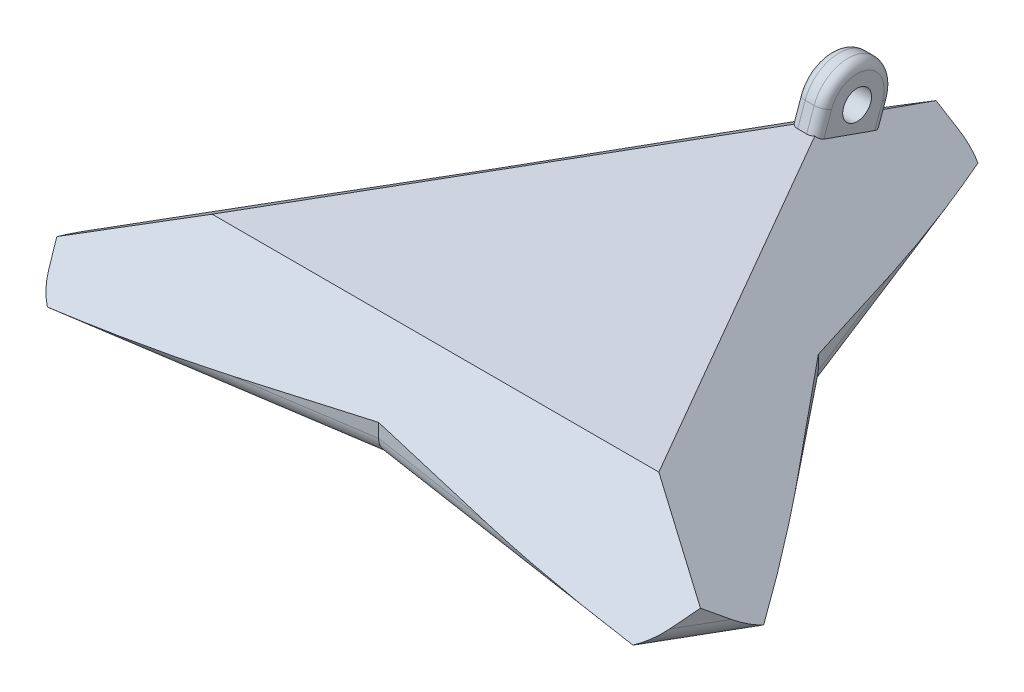
SolidWorks part; units mm, degrees
ref_plane "Front Plane" through (0, 0, 0) normal (0, 0, 1) x (1, 0, 0)
ref_plane "Top Plane" through (0, 0, 0) normal (0, 1, 0) x (1, 0, 0)
ref_plane "Right Plane" through (0, 0, 0) normal (1, 0, 0) x (0, 0, -1)
sketch "Sketch2" plane through (0, 0, 0) normal (0, 1, 0) x (1, 0, 0)
  line L0 (0, 51.9615) -> (-45, -25.9808)
  line L1 (-45, -25.9808) -> (45, -25.9808)
  line L2 (45, -25.9808) -> (0, 51.9615)
  line L3 (0, 0) -> (0, 51.9615) construction
  line L4 (45, -25.9808) -> (0, 0) construction
  line L5 (0, 0) -> (-45, -25.9808) construction
  line L6 (0, 0) -> (0, -25.9808) construction
  line L7 (0, 0) -> (22.5, 12.9904) construction
  line L8 (0, 0) -> (-22.5, 12.9904) construction
  line L9 (10, 34.641) -> (0, 28.8675) construction
  line L10 (0, 28.8675) -> (-10, 34.641) construction
  dimension "D1" = 20
sketch "Sketch3" plane through (0, 0, 0) normal (1, 0, 0) x (0, 0, -1)
  line L0 (-25.9808, 0) -> (-17.3205, 24.4949) construction
  line L1 (-17.3205, 24.4949) -> (0, 18.3712) construction
  line L2 (0, 18.3712) -> (-25.9808, 0) construction
  line L3 (-17.3205, 24.4949) -> (-26.0962, -0.3266) construction
  line L4 (-26.0962, -0.3266) -> (0.2309, 18.2895)
  line L5 (0.2309, 18.2895) -> (-17.3205, 24.4949)
  line L6 (-26.0962, -0.3266) -> (-26.0962, 24.4949)
  line L7 (-26.0962, 24.4949) -> (-17.3205, 24.4949)
  line L8 (0, 0) -> (0, 92.4047) construction
  dimension "D1" = 0.2
ref_plane "Plane1" through (0, 0, 0) normal (0.5, 0, 0.866) x (0.866, 0, -0.5)
sketch "Sketch4" plane through (0, 0, 0) normal (0.5, 0, 0.866) x (0.866, 0, -0.5)
  line L0 (0, 18.3712) -> (17.3205, 24.4949) construction
  line L1 (17.3205, 24.4949) -> (25.9808, 0) construction
  line L2 (25.9808, 0) -> (0, 18.3712) construction
  line L3 (0, 73.4847) -> (0, 0) construction
  line L4 (-0.2309, 18.2895) -> (17.3205, 24.4949)
  line L5 (17.3205, 24.4949) -> (26.0962, -0.3266) construction
  line L6 (26.0962, -0.3266) -> (-0.2309, 18.2895)
  line L7 (17.3205, 24.4949) -> (26.0962, 24.4949)
  line L8 (26.0962, 24.4949) -> (26.0962, -0.3266)
  dimension "D1" = 0.2
ref_plane "Plane2" through (0, 0, 0) normal (0.5, 0, -0.866) x (-0.866, 0, -0.5)
sketch "Sketch5" plane through (0, 0, 0) normal (0.5, 0, -0.866) x (-0.866, 0, -0.5)
  line L0 (17.3205, 24.4949) -> (0, 18.3712) construction
  line L1 (0, 18.3712) -> (25.9808, 0) construction
  line L2 (25.9808, 0) -> (17.3205, 24.4949) construction
  line L3 (17.3205, 24.4949) -> (-0.2309, 18.2895)
  line L4 (-0.2309, 18.2895) -> (26.0962, -0.3266)
  line L5 (26.0962, -0.3266) -> (17.3205, 24.4949) construction
  line L6 (17.3205, 24.4949) -> (26.0962, 24.4949)
  line L7 (26.0962, 24.4949) -> (26.0962, -0.3266)
  dimension "D1" = 0.2
extrude "Boss-Extrude1" add sketch "Sketch2" along normal up to vertex (18.3712 mm away) up to point (0, 18.3712, 0)
extrude "Cut-Extrude2" cut sketch "Sketch3" against normal up to vertex (45 mm away) from vertex up to point (-45, 0, 25.9808) starting at point (45, 0, 25.9808)
extrude "Cut-Extrude3" cut sketch "Sketch4" along normal through all and the other way through all
extrude "Cut-Extrude4" cut sketch "Sketch5" along normal through all from vertex starting at point (-45, 0, 25.9808)
sketch "Sketch6" plane through (0, 0, 0) normal (0, 1, 0) x (1, 0, 0)
  line L0 (0, 0) -> (35.7397, -20.6344) construction
  line L1 (0, 0) -> (-35.7397, -20.6344) construction
  line L2 (0, 0) -> (0, -20.6344) construction
  line L3 (0, 0) -> (0, 41.2687) construction
  line L4 (0, 0) -> (-17.8699, 10.3172) construction
  line L5 (0, 0) -> (17.8699, 10.3172) construction
  line L6 (0, 0) -> (22.5, 12.9904) construction
  line L7 (45, -25.9808) -> (0, 0) construction
  line L8 (44.4, -25.6344) -> (0, 51.2687) construction
  line L9 (35.7397, -20.6344) -> (32.853, -25.6344) construction
  line L10 (0, 51.2687) -> (-44.4, -25.6344) construction
  line L11 (-44.4, -25.6344) -> (44.4, -25.6344) construction
  line L12 (32.853, -25.6344) -> (0, -20.6344)
  line L13 (0, -20.6344) -> (-32.853, -25.6344)
  line L14 (-32.853, -25.6344) -> (-35.7397, -20.6344) construction
  line L15 (-35.7397, -20.6344) -> (-38.6265, -15.6344) construction
  line L16 (-38.6265, -15.6344) -> (-17.8699, 10.3172)
  line L18 (5.7735, 41.2687) -> (-5.7735, 41.2687)
  line L19 (-32.853, -25.6344) -> (-38.6265, -15.6344)
  line L21 (17.8699, 10.3172) -> (38.6265, -15.6344)
  line L22 (38.6265, -15.6344) -> (35.7397, -20.6344) construction
  line L23 (0, 51.2687) -> (44.4, -25.6344) construction
  line L24 (0, 0) -> (0, 51.9615) construction
  line L27 (38.6265, -15.6344) -> (32.853, -25.6344)
  line L35 (45, -25.9808) -> (0, 51.9615) construction
  line L36 (45, -25.9808) -> (0, 51.9615) construction
  line L37 (0, 51.9615) -> (-45, -25.9808) construction
  line L38 (0, 51.9615) -> (-45, -25.9808) construction
  line L46 (17.8699, 10.3172) -> (5.7735, 41.2687)
  line L47 (-5.7735, 41.2687) -> (-17.8699, 10.3172)
  circle A0 centre (0, 0) radius 41.2687 construction
  circle A1 centre (0, 0) radius 20.6344 construction
  circle A2 centre (0, 0) radius 51.2687 construction
  dimension "D1" = 10
  dimension "D2" = 5
extrude "Cut-Extrude5" cut sketch "Sketch6" along normal through all flip side to cut
sketch "Sketch7" plane through (0, 0, 0) normal (1, 0, 0) x (0, 0, -1)
  line L0 (27.2288, 10.3333) -> (23.5754, 0) construction
  line L1 (32.0607, 0) -> (23.5754, 0) construction
  line L2 (34.7712, 7.6667) -> (32.0607, 0) construction
  line L3 (27.2288, 10.3333) -> (23.5754, 0)
  line L4 (32.0607, 0) -> (23.5754, 0)
  line L5 (34.7712, 7.6667) -> (32.0607, 0)
  arc A0 (34.7712, 7.6667) -> (27.2288, 10.3333) centre (31, 9) ccw construction
  arc A1 (34.7712, 7.6667) -> (27.2288, 10.3333) centre (31, 9) ccw
  circle A2 centre (31, 9) radius 1.6 construction
  circle A3 centre (31, 9) radius 1.6 construction
  circle A4 centre (31, 9) radius 4 construction
  circle A5 centre (31, 9) radius 4 construction
sketch "Sketch8" plane through (0, 0, 0) normal (0, 1, 0) x (1, 0, 0)
  line L0 (0, 23.5754) -> (0, 32.0607) construction
  line L1 (-1.5, 23.5754) -> (1.5, 23.5754)
  line L2 (-1.5, 23.5754) -> (-1.5, 32.0607)
  line L3 (-1.5, 32.0607) -> (1.5, 32.0607)
  line L4 (1.5, 23.5754) -> (1.5, 32.0607)
  line L5 (0, 27.818) -> (-1.5, 27.818) construction
  line L6 (0, 27.818) -> (1.5, 27.818) construction
  line L7 (3.7, 23.5754) -> (3.9, 23.5754) construction
  line L8 (1.8, 23.5754) -> (3.7, 23.5754)
  line L9 (1.8, 23.5754) -> (1.8, 32.0607)
  line L10 (1.8, 32.0607) -> (3.7, 32.0607)
  line L11 (3.7, 23.5754) -> (3.7, 32.0607)
  line L12 (-1.8, 23.5754) -> (-3.7, 23.5754)
  line L13 (-1.8, 23.5754) -> (-1.8, 32.0607)
  line L14 (-1.8, 32.0607) -> (-3.7, 32.0607)
  line L15 (-3.7, 23.5754) -> (-3.7, 32.0607)
  line L16 (3.9, 23.5754) -> (3.9, 32.0607) construction
  line L17 (3.9, 32.0607) -> (3.7, 32.0607) construction
  line L18 (-3.7, 32.0607) -> (-3.9, 32.0607) construction
  line L19 (-3.9, 32.0607) -> (-3.9, 23.5754) construction
  line L20 (-3.9, 23.5754) -> (-3.7, 23.5754) construction
  line L21 (-1.8, 23.5754) -> (-1.5, 23.5754) construction
  line L22 (1.8, 23.5754) -> (1.5, 23.5754) construction
  line L23 (-1.8, 32.0607) -> (-1.5, 32.0607) construction
  line L24 (1.5, 32.0607) -> (1.8, 32.0607) construction
  dimension "D1" = 3
  dimension "D2" = 0.3
  dimension "D3" = 0.2
  dimension "D4" = 1.9
ref_plane "Plane3" through (0, 8, 0) normal (0, 1, 0) x (1, 0, 0)
sketch "Sketch10" plane through (0, 8, 0) normal (0, 1, 0) x (1, 0, 0)
  circle A0 centre (0, 0) radius 51.2687 construction
  circle A1 centre (0, 0) radius 51.2687
extrude "Cut-Extrude7" cut sketch "Sketch10" along normal through all
extrude "Boss-Extrude2" add sketch "Sketch7" along normal up to vertex (1.5 mm away) and the other way up to vertex (1.5 mm away) up to point (1.5, 0, -32.0607) other way up to point (-1.5, 0, -32.0607)
sketch "Sketch9" plane through (0, 0, 0) normal (1, 0, 0) x (0, 0, -1)
  circle A0 centre (31, 9) radius 1.6 construction
  circle A1 centre (31, 9) radius 1.6
extrude "Cut-Extrude6" cut sketch "Sketch9" against normal through all and the other way through all
fillet "Fillet1" radius 2 9 edges at (35.7397, 0, 20.6344) (16.4265, 0, 23.1344) (-16.4265, 0, 23.1344) (-35.7397, 0, 20.6344) (-28.2482, 0, 2.6586) (-11.8217, 0, -25.7929) (0, 0, -41.2687) (28.2482, 0, 2.6586) (11.8217, 0, -25.7929)
fillet "Fillet2" radius 1 6 edges at (-1.5, 6.4433, -34.3387) (-1.5, 9.11, -26.7963) (1.5, 6.4433, -34.3387) (1.5, 9.11, -26.7963) (-1.5, 12.7712, -32.3333) (1.5, 12.7712, -32.3333)
ref_plane "Plane7" through (3.7, 0, 0) normal (1, 0, 0) x (0, 0, -1)
sketch "Sketch15" plane through (3.7, 0, 0) normal (1, 0, 0) x (0, 0, -1)
  circle A1 centre (31, 9) radius 2.85 construction
  circle A2 centre (31, 9) radius 2.85 construction
  circle A3 centre (31, 9) radius 3.15
  dimension "D1" = 0.3
ref_plane "Plane8" through (-3.7, 0, 0) normal (1, 0, 0) x (0, 0, -1)
sketch "Sketch16" plane through (-3.7, 0, 0) normal (1, 0, 0) x (0, 0, -1)
  line L0 (29.2391, 12.05) -> (27.4782, 9)
  line L1 (27.4782, 9) -> (29.2391, 5.95)
  line L2 (29.2391, 5.95) -> (32.7609, 5.95)
  line L3 (32.7609, 5.95) -> (34.5218, 9)
  line L4 (34.5218, 9) -> (32.7609, 12.05)
  line L5 (32.7609, 12.05) -> (29.2391, 12.05)
  line L6 (34.1754, 9) -> (32.5877, 11.75)
  line L7 (32.5877, 11.75) -> (29.4123, 11.75)
  line L8 (29.4123, 11.75) -> (27.8246, 9)
  line L9 (27.8246, 9) -> (29.4123, 6.25)
  line L10 (29.4123, 6.25) -> (32.5877, 6.25)
  line L11 (32.5877, 6.25) -> (34.1754, 9)
  line L12 (34.1754, 9) -> (32.5877, 11.75) construction
  line L13 (32.5877, 11.75) -> (29.4123, 11.75) construction
  line L14 (29.4123, 11.75) -> (27.8246, 9) construction
  line L15 (27.8246, 9) -> (29.4123, 6.25) construction
  line L16 (29.4123, 6.25) -> (32.5877, 6.25) construction
  line L17 (32.5877, 6.25) -> (34.1754, 9) construction
  dimension "D1" = 0
  dimension "D2" = 0.3
